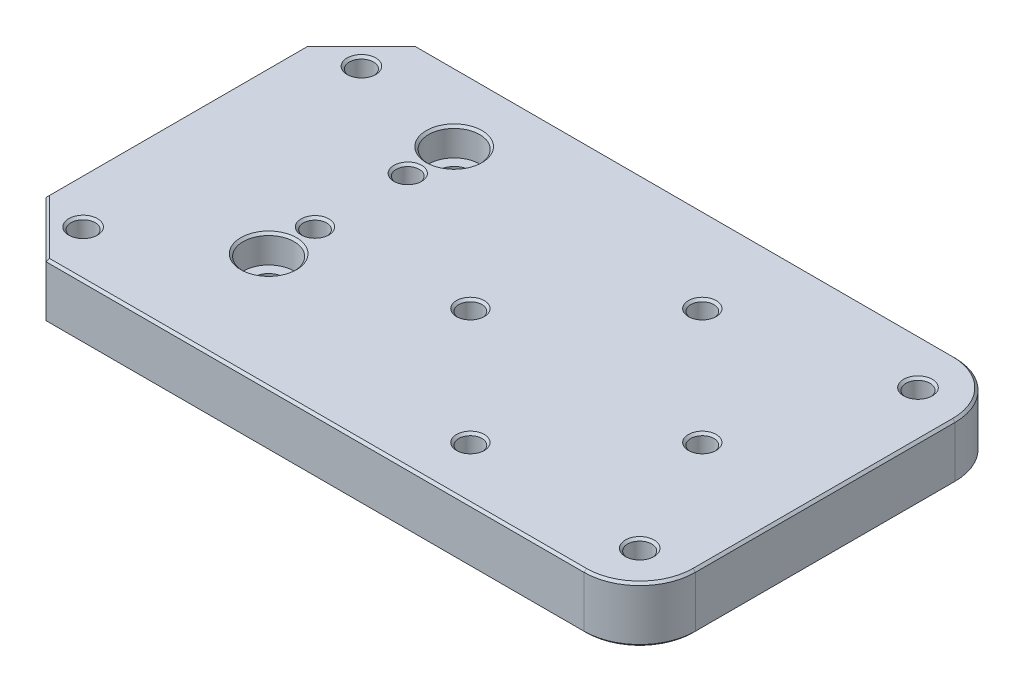
SolidWorks part; units mm, degrees
ref_plane "Front Plane" through (0, 0, 0) normal (0, 0, 1) x (1, 0, 0)
ref_plane "Top Plane" through (0, 0, 0) normal (0, 1, 0) x (1, 0, 0)
ref_plane "Right Plane" through (0, 0, 0) normal (1, 0, 0) x (0, 0, -1)
sketch "Sketch1" plane through (0, 0, 0) normal (0, 1, 0) x (1, 0, 0)
  line L5 (-68, 30) -> (69.8322, 30) construction
  line L6 (-58, 40) -> (58, 40)
  line L7 (-70, 28) -> (-70, -28)
  line L8 (-58, -40) -> (58, -40)
  line L9 (70, 28) -> (70, -28)
  line L11 (-70, 5) -> (70, 5) construction
  line L13 (-70, 0) -> (70, 0) construction
  line L14 (0, 55.6977) -> (0, -52.3255) construction
  line L15 (-70, 28) -> (-58, 40)
  line L16 (-70, -28) -> (-58, -40)
  arc A6 (58, -40) -> (70, -28) centre (58, -28) ccw
  arc A7 (58, 40) -> (70, 28) centre (58, 28) cw
  circle A8 centre (60, 30) radius 2.6
  circle A9 centre (60, -30) radius 2.6
  circle A10 centre (-60, -30) radius 2.6
  circle A11 centre (-60, 30) radius 2.6
  circle A12 centre (22, -3.5) radius 25 construction
  circle A13 centre (22, 21.5) radius 2.5
  circle A14 centre (47, -3.5) radius 2.5
  circle A15 centre (22, -28.5) radius 2.5
  circle A16 centre (-3, -3.5) radius 2.5
  circle A17 centre (-35, 5) radius 5.5
  circle A18 centre (-35, 25) radius 5.5
  circle A19 centre (-35, -15) radius 5.5
  circle A20 centre (-35, 15) radius 2.5
  circle A21 centre (-35, -5) radius 2.5
  point P0 (0, 0)
  point P40 (22, -3.5)
  dimension "D1" = 70
  dimension "D3" = 12
  dimension "D5" = 5.2
  dimension "D12" = 50
  dimension "D13" = 5
  dimension "D16" = 11
  dimension "D20" = 5
  dimension "D2" = 140
  dimension "D4" = 10
  dimension "D6" = 60
  dimension "D7" = 45
  dimension "D8" = 12
  dimension "D9" = 60
  dimension "D10" = 36.5
  dimension "D11" = 48
  dimension "D15" = 35
  dimension "D17" = 35
  dimension "D19" = 20
  dimension "D21" = 10
  dimension "D18" = 2
  dimension "D14" = 4
extrude "Boss-Extrude1" add sketch "Sketch1" along normal mid plane 12 contours A7 L6 L15 L7 L16 L8 A6 L9 A19 A18 A17 A16 A15 A14 A13 A9 A8 A10 A11 A20 A21 | A19 | A17 | A18 region at (1.4247, 0, 0.1282) region at (-35, 0, -5) region at (-35, 0, -25) region at (-35, 0, 15)
extrude "Cut-Extrude1" cut sketch "Sketch1<3>" along normal blind 6 contours A18 | A19 region at (-35, 0, -25) region at (-35, 0, 15)
sketch "Sketch1<3>" plane through (0, 0, 0) normal (0, 1, 0) x (1, 0, 0) same geometry as "Sketch1"
sketch "Sketch2" plane through (0, 0, 0) normal (0, 1, 0) x (1, 0, 0)
  line L0 (-70, 5) -> (70, 5) construction
  line L1 (-70, 28) -> (-70, -28) construction
  line L2 (70, 28) -> (70, -28) construction
  line L3 (-58, 40) -> (58, 40) construction
  circle A0 centre (-35, 25) radius 3.25
  circle A1 centre (-35, -15) radius 3.25
  dimension "D1" = 6.5
  dimension "35" = 35
extrude "Cut-Extrude2" cut sketch "Sketch2" against normal blind 6
extrude "Cut-Extrude3" cut sketch "Sketch1<4>" against normal blind 4.5 from offset 4.5 contours A17 offset against normal yes
sketch "Sketch1<4>" plane through (0, 0, 0) normal (0, 1, 0) x (1, 0, 0) same geometry as "Sketch1"
hole_wizard "#6 (0.2361) Diameter Hole1" positions "Sketch4" profile "Sketch5" hole size "#6" standard "ANSI Inch"
sketch "Sketch4" plane through (0, -4.5, 0) normal (0, -1, 0) x (-1, 0, 0)
  point P0 (35, 5)
sketch "Sketch5" plane through (-35, -4.5, -5) normal (1, 0, 0) x (0, 0, -1)
  line L0 (0, 0) -> (0, 4.5)
  line L1 (0, 4.5) -> (2.9985, 2.6983)
  line L2 (2.9985, 2.6983) -> (2.9985, 0)
  line L5 (2.9985, 0) -> (0, 0)
  line L10 (0, 4.5) -> (-2.9985, 2.6983) construction
  line L11 (0, -6.35) -> (0, 107.95) construction
  dimension "Hole Dia." = 5.9969
  dimension "Hole Depth" = 4.5
  dimension "Drill Angle" = 118
sketch "Sketch6" plane through (0, 6, 0) normal (0, 1, 0) x (1, 0, 0)
  line L0 (-35, 5) -> (70, 5)
  line L1 (70, 28) -> (70, -28) construction
  line L2 (14, 40) -> (14, -40)
  line L3 (-58, 40) -> (58, 40) construction
  line L4 (-58, -40) -> (58, -40) construction
  line L5 (-70, 28) -> (-70, -28) construction
  dimension "D1" = 84
hole_wizard "#6 (0.2361) Diameter Hole4" positions "Sketch13" profile "Sketch14" hole size "#6" standard "ANSI Inch"
sketch "Sketch13" plane through (0, -6, 0) normal (0, -1, 0) x (-1, 0, 0)
  line L0 (35, 5) -> (-70, 5) construction
  line L1 (-14, 40) -> (-14, -40) construction
  point P0 (-14, 5)
sketch "Sketch14" plane through (14, -6, -5) normal (1, 0, 0) x (0, 0, -1)
  line L0 (0, 0) -> (0, 6)
  line L1 (0, 6) -> (2.9985, 4.1983)
  line L2 (2.9985, 4.1983) -> (2.9985, 0)
  line L5 (2.9985, 0) -> (0, 0)
  line L10 (0, 6) -> (-2.9985, 4.1983) construction
  line L11 (0, -6.35) -> (0, 107.95) construction
  dimension "Hole Dia." = 5.9969
  dimension "Hole Depth" = 6
  dimension "Drill Angle" = 118
sketch "Sketch9" plane through (-70, 0, 0) normal (-1, 0, 0) x (0, 0, 1)
  line L0 (-40, 6) -> (-40, -6) construction
  circle A0 centre (-5, 0) radius 4
  dimension "D1" = 8
  dimension "D2" = 35
extrude "Cut-Extrude4" cut sketch "Sketch9" against normal blind 15
sketch "Sketch10" plane through (-55, 0, 0) normal (-1, 0, 0) x (0, 0, 1)
  circle A0 centre (-5, 0) radius 3
  dimension "D1" = 6
hole_wizard "#6 (0.2361) Diameter Hole3" positions "Sketch11" profile "Sketch12" hole size "#6" standard "ANSI Inch"
sketch "Sketch11" plane through (-55, 0, 0) normal (-1, 0, 0) x (0, 0, 1)
  point P0 (-5, 0)
sketch "Sketch12" plane through (-55, 0, -5) normal (0, 1, 0) x (0, 0, 1)
  line L0 (0, 0) -> (0, 74.8017)
  line L1 (0, 74.8017) -> (2.9985, 73)
  line L2 (2.9985, 73) -> (2.9985, 0)
  line L5 (2.9985, 0) -> (0, 0)
  line L10 (0, 74.8017) -> (-2.9985, 73) construction
  line L11 (0, -6.35) -> (0, 107.95) construction
  dimension "Hole Dia." = 5.9969
  dimension "Hole Depth" = 73
  dimension "Drill Angle" = 118
chamfer "Chamfer1" distance 0.5 angle 45 20 edges at (-35, 6, 7.5) (-35, 6, -12.5) (-60, 6, -27.4) (-60, 6, 32.6) (70, 6, 0) (66.4853, 6, 36.4853) (0, 6, 40) (-64, 6, 34) (-70, 6, 0) (-64, 6, -34) (0, 6, -40) (66.4853, 6, -36.4853) (60, 6, -27.4) (60, 6, 32.6) (22, 6, -19) (47, 6, 6) (22, 6, 31) (-3, 6, 6) (-35, 6, -19.5) (-35, 6, 20.5)
chamfer "Chamfer2" distance 0.5 angle 45 22 edges at (-35, -6, 7.5) (-35, -6, -12.5) (-60, -6, -27.4) (-60, -6, 32.6) (0, -6, -40) (-64, -6, -34) (-70, -6, 0) (-64, -6, 34) (0, -6, 40) (66.4853, -6, 36.4853) (70, -6, 0) (66.4853, -6, -36.4853) (60, -6, -27.4) (60, -6, 32.6) (22, -6, -19) (47, -6, 6) (22, -6, 31) (-3, -6, 6) (-35, -6, 11.75) (-35, -6, -21.75) (-35, -6, 0.5) (14, -6, -7.9985)
